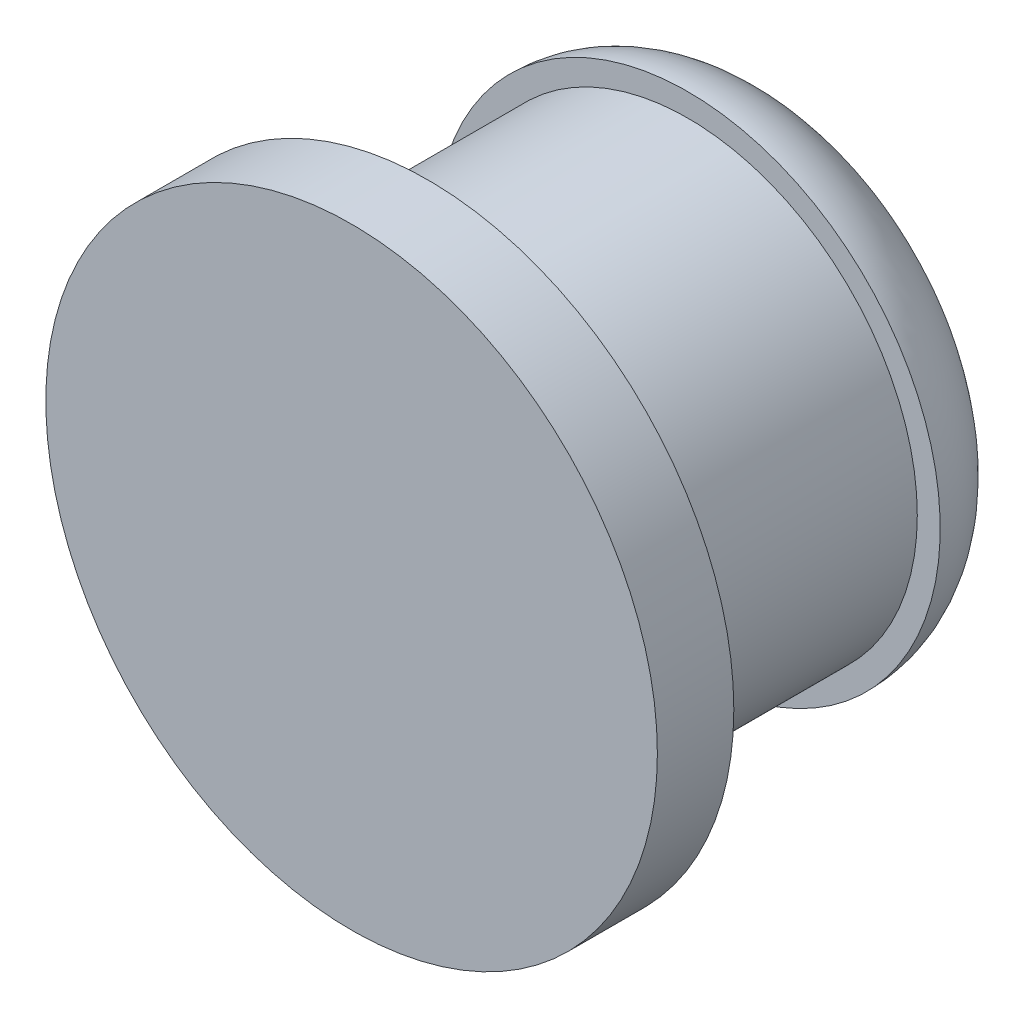
SolidWorks part; units mm, degrees
ref_plane "Ön Düzlem" through (0, 0, 0) normal (0, 0, 1) x (1, 0, 0)
ref_plane "Üst Düzlem" through (0, 0, 0) normal (0, 1, 0) x (1, 0, 0)
ref_plane "Sağ Düzlem" through (0, 0, 0) normal (1, 0, 0) x (0, 0, -1)
sketch "Çizim1" plane through (0, 0, 0) normal (0, 0, 1) x (1, 0, 0)
  circle A0 centre (21.5715, 0) radius 2
  dimension "D1" = 4
extrude "Yükseklik-Ekstrüzyon1" add sketch "Çizim1" along normal blind 0.5
sketch "Çizim2" plane through (0, 0, 0) normal (0, 0, -1) x (-1, 0, 0)
  circle A0 centre (-21.5715, 0) radius 1.5
  dimension "D1" = 3
extrude "Yükseklik-Ekstrüzyon2" add sketch "Çizim2" along normal blind 1.7
sketch "Çizim3" plane through (0, 0, -1.7) normal (0, 0, -1) x (-1, 0, 0)
  circle A0 centre (-21.5715, 0) radius 1.65
  dimension "D1" = 3.3
extrude "Yükseklik-Ekstrüzyon3" add sketch "Çizim3" along normal blind 0.6
fillet "Radyus1" radius 0.6 1 edges at (19.9215, 0, -2.3)
